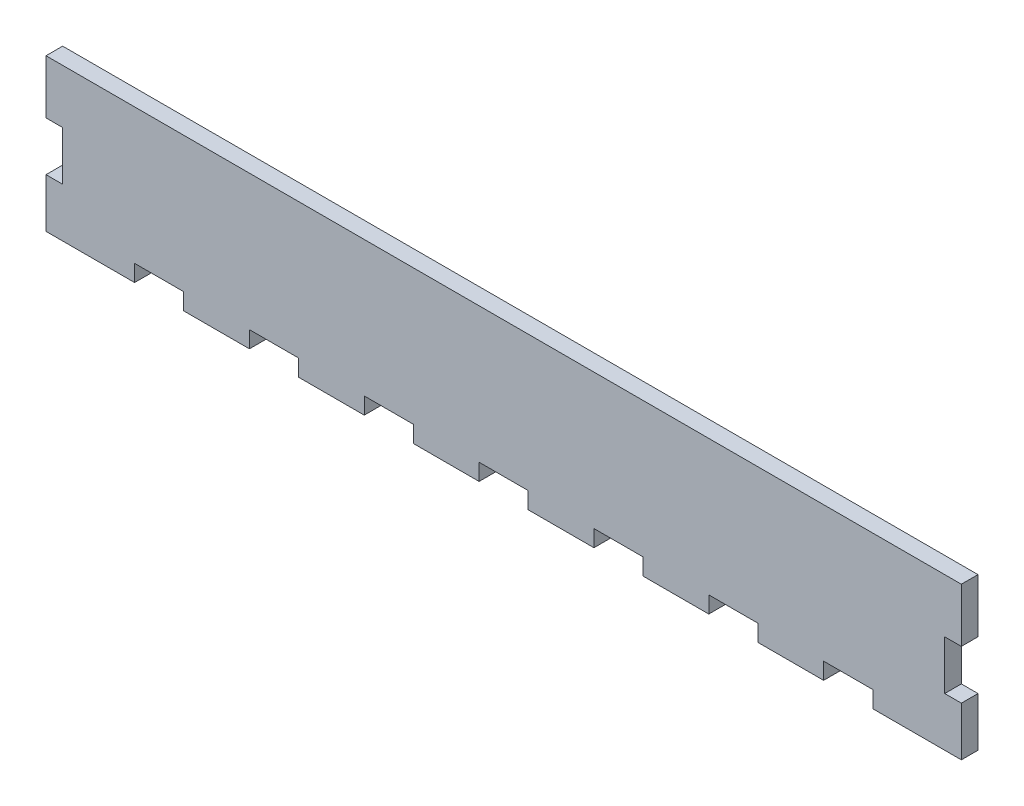
SolidWorks part; units mm, degrees
ref_plane "Front Plane" through (0, 0, 0) normal (0, 0, 1) x (1, 0, 0)
ref_plane "Top Plane" through (0, 0, 0) normal (0, 1, 0) x (1, 0, 0)
ref_plane "Right Plane" through (0, 0, 0) normal (1, 0, 0) x (0, 0, -1)
sketch "Sketch27" plane through (0, 0, 0) normal (0, 0, 1) x (1, 0, 0)
  line L0 (-5.08, -266.0731) -> (21.9637, -266.073)
  line L1 (36.9637, -266.073) -> (57.0157, -266.073)
  line L2 (-5.08, -266.0731) -> (-5.08, -251.0731)
  line L3 (-5.08, -219.6339) -> (274.32, -219.6339)
  line L4 (274.32, -266.0731) -> (274.32, -251.0731)
  line L5 (72.0157, -266.073) -> (92.0677, -266.073)
  line L6 (107.0677, -266.073) -> (127.1197, -266.073)
  line L7 (-5.08, -251.0731) -> (0, -251.0731)
  line L8 (-5.08, -236.0731) -> (-5.08, -219.6339)
  line L9 (-5.08, -236.0731) -> (0, -236.0731)
  line L10 (21.9637, -260.993) -> (36.9637, -260.993)
  line L11 (21.9637, -260.993) -> (21.9637, -266.073)
  line L12 (142.1197, -266.073) -> (162.1717, -266.073)
  line L13 (274.32, -236.0731) -> (274.32, -219.6339)
  line L14 (36.9637, -260.993) -> (36.9637, -266.073)
  line L15 (274.32, -251.0731) -> (269.24, -251.0731)
  line L16 (57.0157, -260.993) -> (72.0157, -260.993)
  line L17 (274.32, -236.0731) -> (269.24, -236.0731)
  line L18 (0, -236.0731) -> (0, -251.0731)
  line L19 (177.1717, -266.073) -> (197.2237, -266.073)
  line L20 (269.24, -236.0731) -> (269.24, -251.0731)
  line L21 (57.0157, -260.993) -> (57.0157, -266.073)
  line L22 (72.0157, -260.993) -> (72.0157, -266.073)
  line L23 (92.0677, -260.993) -> (92.0677, -266.073)
  line L24 (92.0677, -260.993) -> (107.0677, -260.993)
  line L25 (212.2237, -266.073) -> (232.2757, -266.073)
  line L26 (107.0677, -260.993) -> (107.0677, -266.073)
  line L27 (127.1197, -260.993) -> (127.1197, -266.073)
  line L28 (127.1197, -260.993) -> (142.1197, -260.993)
  line L30 (142.1197, -260.993) -> (142.1197, -266.073)
  line L31 (162.1717, -260.993) -> (162.1717, -266.073)
  line L32 (162.1717, -260.993) -> (177.1717, -260.993)
  line L33 (247.2757, -266.073) -> (274.32, -266.0731)
  line L34 (177.1717, -260.993) -> (177.1717, -266.073)
  line L35 (197.2237, -260.993) -> (197.2237, -266.073)
  line L36 (197.2237, -260.993) -> (212.2237, -260.993)
  line L38 (212.2237, -260.993) -> (212.2237, -266.073)
  line L39 (232.2757, -260.993) -> (232.2757, -266.073)
  line L40 (232.2757, -260.993) -> (247.2757, -260.993)
  line L42 (247.2757, -260.993) -> (247.2757, -266.073)
  dimension "D1" = 279.4
extrude "Boss-Extrude1" add sketch "Sketch27" along normal blind 5.08
